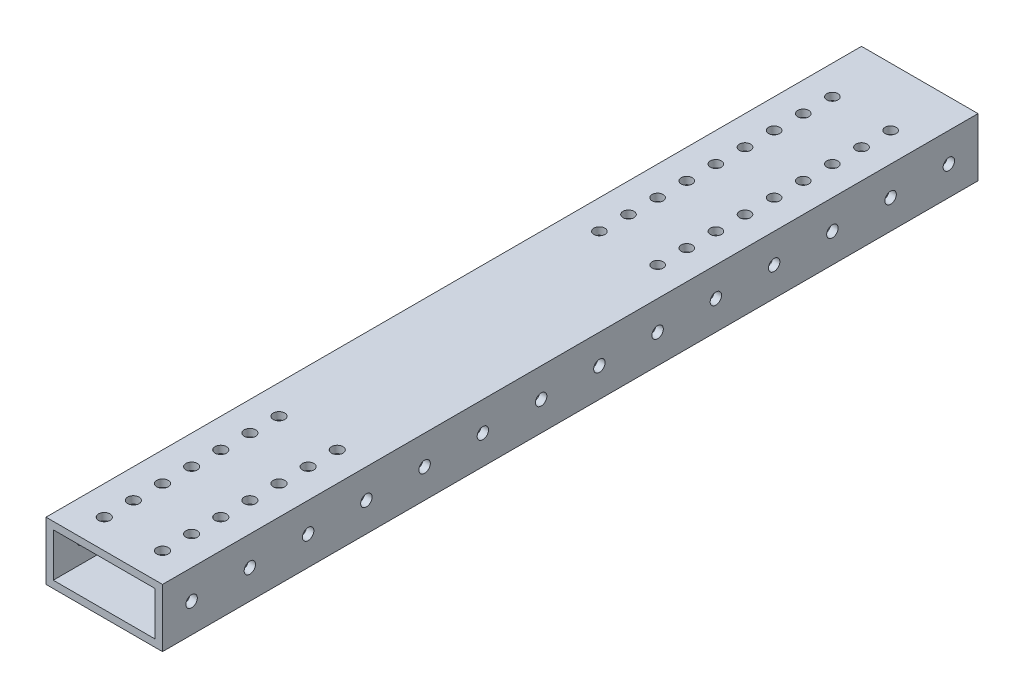
SolidWorks part; units mm, degrees
material "6061-T6 (SS)"
ref_plane "Front Plane" through (0, 0, 0) normal (0, 0, 1) x (1, 0, 0)
ref_plane "Top Plane" through (0, 0, 0) normal (0, 1, 0) x (1, 0, 0)
ref_plane "Right Plane" through (0, 0, 0) normal (1, 0, 0) x (0, 0, -1)
sketch "Sketch1" plane through (0, 0, 0) normal (0, 0, 1) x (1, 0, 0)
  line L0 (-22.225, 9.525) -> (22.225, 9.525)
  line L1 (-25.4, 12.7) -> (25.4, 12.7)
  line L2 (-25.4, 12.7) -> (-25.4, -12.7)
  line L3 (-25.4, -12.7) -> (25.4, -12.7)
  line L4 (25.4, 12.7) -> (25.4, -12.7)
  line L5 (22.225, 9.525) -> (22.225, -9.525)
  line L6 (-22.225, -9.525) -> (22.225, -9.525)
  line L7 (-22.225, 9.525) -> (-22.225, -9.525)
  line L8 (-25.4, 12.7) -> (25.4, -12.7) construction
  line L9 (25.4, 12.7) -> (-25.4, -12.7) construction
  point P5 (0, 0)
  dimension "D1" = 50.8
  dimension "D2" = 25.4
  dimension "D3" = 3.175
extrude "Boss-Extrude1" add sketch "Sketch1" along normal mid plane 355.6
sketch "Sketch2" plane through (0, 12.7, 0) normal (0, -1, 0) x (1, 0, 0)
  circle A36 centre (-12.7, 165.1) radius 2.4892 construction
  circle A37 centre (-12.7, 152.4) radius 2.4892 construction
  circle A38 centre (-12.7, 139.7) radius 2.4892 construction
  circle A39 centre (-12.7, 127) radius 2.4892 construction
  circle A40 centre (-12.7, 114.3) radius 2.4892 construction
  circle A41 centre (-12.7, 101.6) radius 2.4892 construction
  circle A42 centre (-12.7, 88.9) radius 2.4892 construction
  circle A50 centre (12.7, 165.1) radius 2.4892 construction
  circle A51 centre (12.7, 152.4) radius 2.4892 construction
  circle A52 centre (12.7, 139.7) radius 2.4892 construction
  circle A53 centre (12.7, 127) radius 2.4892 construction
  circle A54 centre (12.7, 114.3) radius 2.4892 construction
  circle A55 centre (12.7, 101.6) radius 2.4892 construction
  circle A56 centre (12.7, 88.9) radius 2.4892 construction
  circle A57 centre (-12.7, 165.1) radius 2.4892
  circle A58 centre (-12.7, 152.4) radius 2.4892
  circle A59 centre (-12.7, 139.7) radius 2.4892
  circle A60 centre (-12.7, 127) radius 2.4892
  circle A61 centre (-12.7, 114.3) radius 2.4892
  circle A62 centre (-12.7, 101.6) radius 2.4892
  circle A63 centre (-12.7, 88.9) radius 2.4892
  circle A71 centre (12.7, 165.1) radius 2.4892
  circle A72 centre (12.7, 152.4) radius 2.4892
  circle A73 centre (12.7, 139.7) radius 2.4892
  circle A74 centre (12.7, 127) radius 2.4892
  circle A75 centre (12.7, 114.3) radius 2.4892
  circle A76 centre (12.7, 101.6) radius 2.4892
  circle A77 centre (12.7, 88.9) radius 2.4892
extrude "Cut-Extrude1" cut sketch "Sketch2" along normal up to next
sketch "Sketch3" plane through (25.4, 0, 0) normal (1, 0, 0) x (0, 0, -1)
  line L0 (-177.8, 0) -> (177.8, 0) construction
  line L1 (-177.8, -12.7) -> (-177.8, 12.7) construction
  line L2 (177.8, -12.7) -> (177.8, 12.7) construction
  circle A0 centre (-165.1, 0) radius 2.4892
  circle A1 centre (-139.7, 0) radius 2.4892
  circle A2 centre (-114.3, 0) radius 2.4892
  circle A3 centre (-88.9, 0) radius 2.4892
  circle A4 centre (-63.5, 0) radius 2.4892
  circle A5 centre (-38.1, 0) radius 2.4892
  circle A6 centre (-12.7, 0) radius 2.4892
  circle A7 centre (12.7, 0) radius 2.4892
  circle A8 centre (38.1, 0) radius 2.4892
  circle A9 centre (63.5, 0) radius 2.4892
  circle A10 centre (88.9, 0) radius 2.4892
  circle A11 centre (114.3, 0) radius 2.4892
  circle A12 centre (139.7, 0) radius 2.4892
  circle A13 centre (165.1, 0) radius 2.4892
  dimension "D1" = 4.9784
  dimension "D2" = 12.7
  dimension "D4" = 25.4
  dimension "D3" = 14
extrude "Cut-Extrude2" cut sketch "Sketch3" against normal through all
sketch "Sketch4" plane through (0, -12.7, 0) normal (0, -1, 0) x (1, 0, 0)
  circle A0 centre (-12.7, -152.4) radius 2.413 construction
  circle A1 centre (-12.7, -139.7) radius 2.413 construction
  circle A2 centre (-12.7, -127) radius 2.413 construction
  circle A3 centre (-12.7, -114.3) radius 2.413 construction
  circle A4 centre (-12.7, -101.6) radius 2.413 construction
  circle A5 centre (-12.7, -88.9) radius 2.413 construction
  circle A6 centre (-12.7, -76.2) radius 2.413 construction
  circle A7 centre (-12.7, -63.5) radius 2.413 construction
  circle A8 centre (-12.7, -50.8) radius 2.413 construction
  circle A9 centre (12.7, -50.8) radius 2.413 construction
  circle A10 centre (12.7, -63.5) radius 2.413 construction
  circle A11 centre (12.7, -76.2) radius 2.413 construction
  circle A12 centre (12.7, -88.9) radius 2.413 construction
  circle A13 centre (12.7, -101.6) radius 2.413 construction
  circle A14 centre (12.7, -114.3) radius 2.413 construction
  circle A15 centre (12.7, -127) radius 2.413 construction
  circle A16 centre (12.7, -139.7) radius 2.413 construction
  circle A17 centre (12.7, -152.4) radius 2.413 construction
  circle A18 centre (-12.7, -152.4) radius 2.413
  circle A19 centre (-12.7, -139.7) radius 2.413
  circle A20 centre (-12.7, -127) radius 2.413
  circle A21 centre (-12.7, -114.3) radius 2.413
  circle A22 centre (-12.7, -101.6) radius 2.413
  circle A23 centre (-12.7, -88.9) radius 2.413
  circle A24 centre (-12.7, -76.2) radius 2.413
  circle A25 centre (-12.7, -63.5) radius 2.413
  circle A26 centre (-12.7, -50.8) radius 2.413
  circle A27 centre (12.7, -50.8) radius 2.413
  circle A28 centre (12.7, -63.5) radius 2.413
  circle A29 centre (12.7, -76.2) radius 2.413
  circle A30 centre (12.7, -88.9) radius 2.413
  circle A31 centre (12.7, -101.6) radius 2.413
  circle A32 centre (12.7, -114.3) radius 2.413
  circle A33 centre (12.7, -127) radius 2.413
  circle A34 centre (12.7, -139.7) radius 2.413
  circle A35 centre (12.7, -152.4) radius 2.413
extrude "Cut-Extrude3" cut sketch "Sketch4" against normal through all
